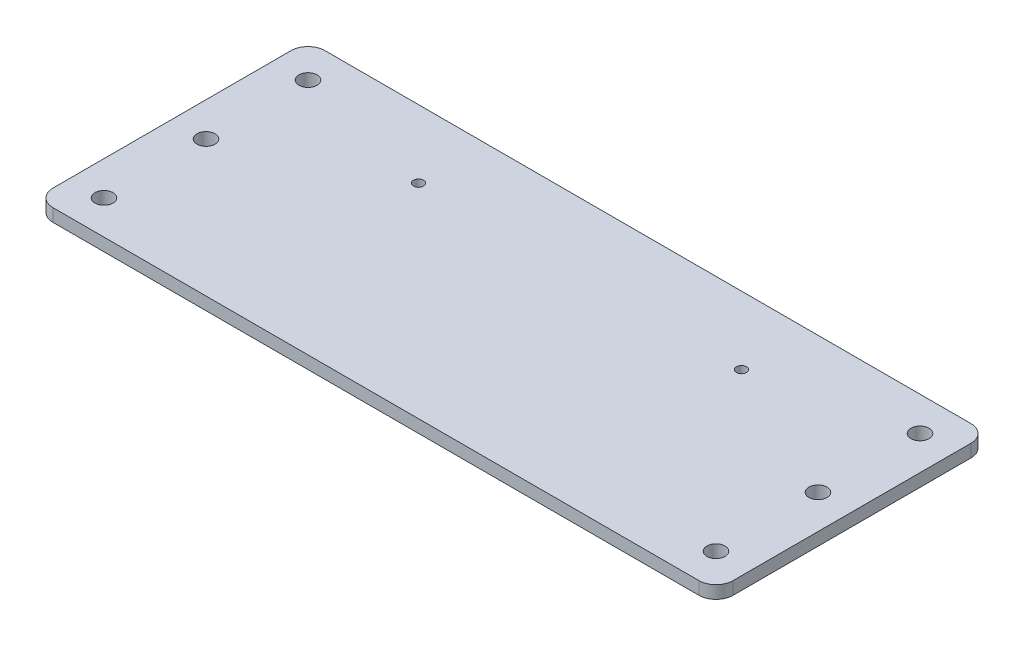
SolidWorks part; units mm, degrees
ref_plane "Front Plane" through (0, 0, 0) normal (0, 0, 1) x (1, 0, 0)
ref_plane "Top Plane" through (0, 0, 0) normal (0, 1, 0) x (1, 0, 0)
ref_plane "Right Plane" through (0, 0, 0) normal (1, 0, 0) x (0, 0, -1)
sketch "Sketch2" plane through (0, 0, 0) normal (0, 1, 0) x (1, 0, 0)
  line L1 (0, 0) -> (254, 0)
  line L2 (0, 0) -> (0, -101.6)
  line L3 (0, -101.6) -> (254, -101.6)
  line L4 (254, 0) -> (254, -101.6)
  point P5 (66.675, -25.4)
  point P6 (187.325, -25.4)
  point P7 (12.7, -88.9)
  point P8 (12.7, -12.7)
  point P9 (241.3, -88.9)
  point P10 (241.3, -12.7)
  point P11 (241.3, -50.8)
  point P12 (0, 0)
  point P13 (0, 0)
  point P14 (0, 0)
  point P15 (12.7, -50.8)
  dimension "D1" = 101.6
  dimension "D2" = 254
  dimension "D3" = 120.65
  dimension "D4" = 66.675
  dimension "D5" = 25.4
  dimension "D6" = 12.7
  dimension "D7" = 12.7
  dimension "D8" = 12.7
  dimension "D9" = 12.7
  dimension "D10" = 38.1
extrude "Boss-Extrude1" add sketch "Sketch2" along normal blind 4.7625
fillet "Fillet1" radius 6.35 4 edges at (254, 2.3813, 0) (254, 2.3813, 101.6) (0, 2.3813, 101.6) (0, 2.3813, 0)
hole_wizard "#6 Clearance Hole1" positions "Sketch3" profile "Sketch4" hole size "#6" standard "ANSI Inch" end condition through all
sketch "Sketch3" plane through (0, 4.7625, 0) normal (0, 1, 0) x (1, 0, 0)
  point P0 (66.675, -25.4)
  point P3 (187.325, -25.4)
sketch "Sketch4" plane through (66.675, 4.7625, 25.4) normal (1, 0, 0) x (0, 0, 1)
  line L0 (0, 0) -> (0, 4.7625)
  line L1 (0, 4.7625) -> (1.8986, 4.7625)
  line L2 (1.8986, 4.7625) -> (1.8986, 0)
  line L5 (1.8986, 0) -> (0, 0)
  line L11 (0, -6.35) -> (0, 107.95) construction
  dimension "Thru Hole Dia." = 3.7973
  dimension "Thru Hole Depth" = 4.7625
hole_wizard "1/4 Clearance Hole1" positions "Sketch5" profile "Sketch6" hole size "1/4" standard "ANSI Inch" end condition through all
sketch "Sketch5" plane through (0, 4.7625, 0) normal (0, 1, 0) x (1, 0, 0)
  point P0 (12.7, -12.7)
  point P3 (12.7, -88.9)
  point P6 (241.3, -88.9)
  point P9 (241.3, -12.7)
  point P13 (12.7, -50.8)
  point P16 (241.3, -50.8)
sketch "Sketch6" plane through (12.7, 4.7625, 12.7) normal (1, 0, 0) x (0, 0, 1)
  line L0 (0, 0) -> (0, 4.7625)
  line L1 (0, 4.7625) -> (3.3782, 4.7625)
  line L2 (3.3782, 4.7625) -> (3.3782, 0)
  line L5 (3.3782, 0) -> (0, 0)
  line L11 (0, -6.35) -> (0, 107.95) construction
  dimension "Thru Hole Dia." = 6.7564
  dimension "Thru Hole Depth" = 4.7625
